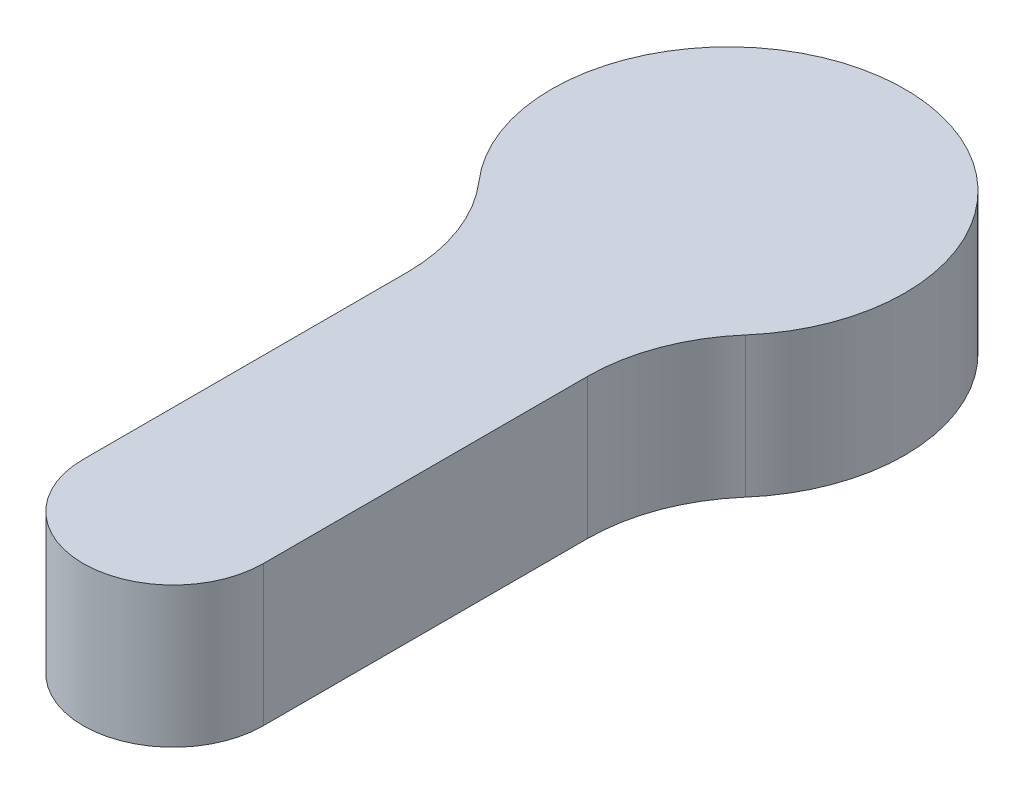
SolidWorks part; units mm, degrees
ref_plane "Front Plane" through (0, 0, 0) normal (0, 0, 1) x (1, 0, 0)
ref_plane "Top Plane" through (0, 0, 0) normal (0, 1, 0) x (1, 0, 0)
ref_plane "Right Plane" through (0, 0, 0) normal (1, 0, 0) x (0, 0, -1)
sketch "Sketch2" plane through (0, 0, 0) normal (0, 1, 0) x (1, 0, 0)
  line L2 (-3.7973, -13.6512) -> (-3.7973, 0)
  line L4 (3.7973, -13.6512) -> (3.7973, 0)
  arc A1 (5.6104, 4.8397) -> (-5.6104, 4.8397) centre (0, 9.7295) ccw
  arc A2 (-3.7973, -13.6512) -> (3.7973, -13.6512) centre (0, -13.6512) ccw
  arc A3 (3.7973, 0) -> (5.6104, 4.8397) centre (11.1633, 0) cw
  arc A4 (-3.7973, 0) -> (-5.6104, 4.8397) centre (-11.1633, 0) ccw
  point P0 (0, 0)
  point P4 (0, -17.4485)
  point P10 (0, 17.1717)
  dimension "D2" = 34.6202
  dimension "D3" = 7.366
  dimension "D4" = 7.4422
  dimension "D1" = 7.5946
extrude "Boss-Extrude1" add sketch "Sketch2" along normal blind 5.9182
